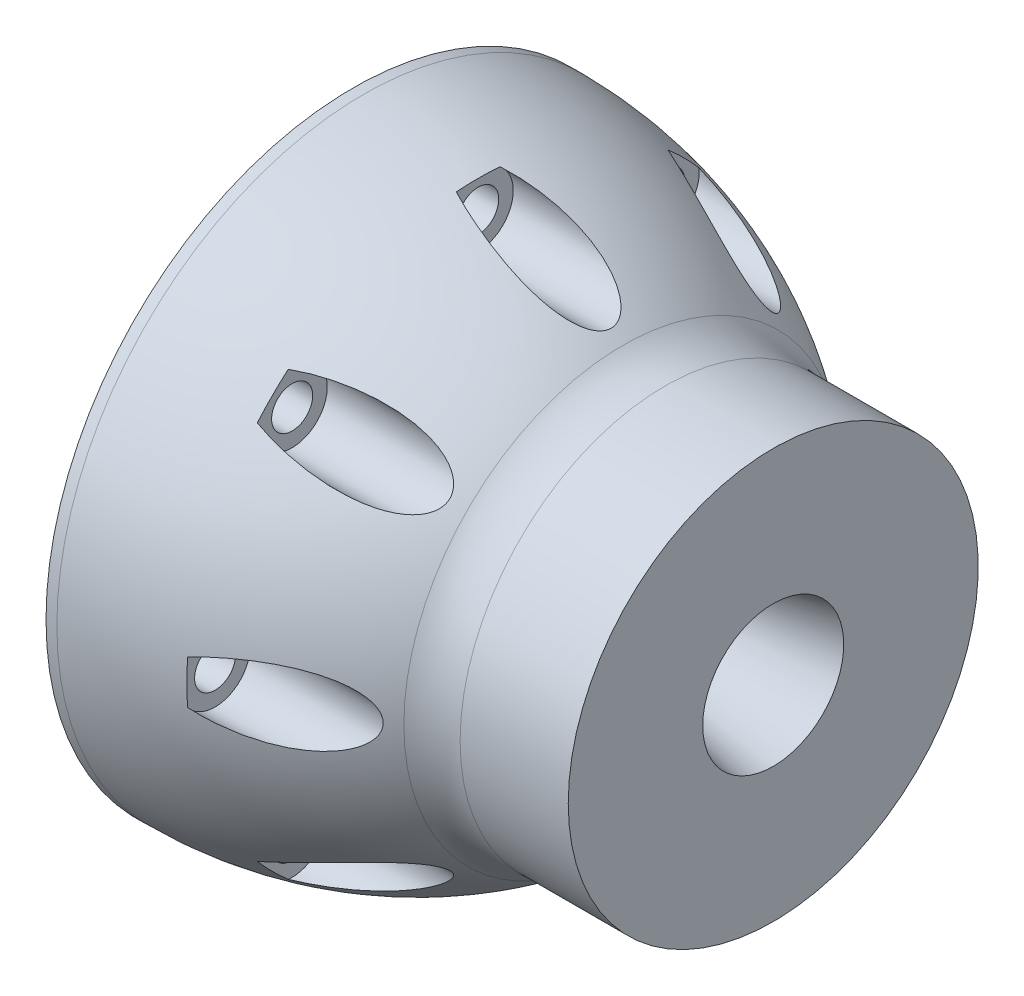
SolidWorks part; units mm, degrees
ref_plane "Front Plane" through (0, 0, 0) normal (0, 0, 1) x (1, 0, 0)
ref_plane "Top Plane" through (0, 0, 0) normal (0, 1, 0) x (1, 0, 0)
ref_plane "Right Plane" through (0, 0, 0) normal (1, 0, 0) x (0, 0, -1)
sketch "Model" plane through (0, 0, 0) normal (0, 0, 1) x (1, 0, 0)
  line L0 (0, 19.051) -> (31.9536, 19.051)
  line L1 (38.3809, 16.3887) -> (49.0299, 5.7397)
  line L2 (0, 0) -> (61.8717, 0) construction
  arc A0 (38.3809, 16.3887) -> (31.9536, 19.051) centre (31.9536, 9.9615) ccw
  arc A1 (49.0299, 5.7397) -> (50.8, 5.0065) centre (50.8, 7.5097) ccw
  arc A2 (50.8, 5.0065) -> (51.2904, 5.055) centre (50.8, 7.5097) ccw
  spline S0 degree 2 poles (51.2904, 5.055) (61.5184, 7.0984) (61.8717, 7.148) knots 0 0 0 1 1 1
  text T0 "Vortex_Chamber_Cold_Wall" font "SWTXT" height 5
sketch "Sketch2" plane through (0, 0, 0) normal (0, 0, 1) x (1, 0, 0)
  line L0 (61.8717, 7.148) -> (51.2904, 5.055)
  line L1 (49.0299, 5.7397) -> (38.3809, 16.3887)
  line L2 (31.9536, 19.051) -> (25.6036, 19.051)
  line L3 (0, 19.051) -> (31.9536, 19.051) construction
  line L4 (25.6036, 19.051) -> (25.6036, 22.225)
  line L5 (0, 0) -> (61.8717, 0) construction
  line L6 (25.6036, 22.225) -> (19.2536, 22.225)
  line L7 (19.2536, 22.225) -> (19.2536, 31.115)
  line L8 (19.2536, 31.115) -> (20.3519, 31.115)
  line L9 (50.9079, 20.7844) -> (61.8717, 20.7844)
  line L10 (61.8717, 20.7844) -> (61.8717, 7.148)
  arc A0 (51.2904, 5.055) -> (50.8, 5.0065) centre (50.7951, 7.5588) cw
  arc A1 (50.8, 5.0065) -> (49.0299, 5.7397) centre (50.7953, 7.4983) cw
  arc A2 (38.3809, 16.3887) -> (31.9536, 19.051) centre (31.9536, 9.9614) ccw
  arc A3 (20.3519, 31.115) -> (46.6468, 22.225) centre (20.3519, -12.2178) cw
  arc A4 (46.6468, 22.225) -> (50.9079, 20.7844) centre (50.9079, 27.8064) ccw
  point P21 (19.2536, 26.67)
  point P29 (41.1566, 25.4031)
  point P31 (50.307, 23.0502)
  point P32 (41.2438, 25.4903)
  point P33 (52.0499, 20.7844)
  point P34 (43.5096, 24.2702)
  point P35 (46.6468, 22.225)
  dimension "D1" = 6.35
  dimension "D2" = 22.225
  dimension "D3" = 26.67
  dimension "D4" = 6.35
revolve "Revolve1" add sketch "Sketch2" angle 360 about L2
sketch "Sketch3" plane through (19.2536, 0, 0) normal (-1, 0, 0) x (0, 0, 1)
  line L0 (0, 22.225) -> (0, 31.115) construction
  circle A0 centre (0, 26.67) radius 3.556
  circle A1 centre (0, 0) radius 22.225 construction
  circle A2 centre (0, 0) radius 22.225 construction
  circle A3 centre (0, 0) radius 31.115 construction
  point P11 (0, 26.67)
  dimension "D1" = 7.112
extrude "Cut-Extrude1" cut sketch "Sketch3" against normal up to surface (42.6182 mm away) from offset 12.7 up to face at (61.8717, 0, 20.7844) offset against normal yes
sketch "Sketch4" plane through (31.9536, 0, 0) normal (1, 0, 0) x (0, 0, -1)
  circle A0 centre (0, 26.67) radius 2.0828
  dimension "D1" = 4.1656
extrude "Cut-Extrude2" cut sketch "Sketch4" against normal up to surface (12.7 mm away) up to face at (19.2536, 0, 22.225)
pattern_circular "CirPattern1" count 8 over 360 about axis through (0, 0, 0) along (1, 0, 0) of "Cut-Extrude2", "Cut-Extrude1"
sketch "Sketch5" plane through (0, 0, 0) normal (0, 0, 1) x (1, 0, 0)
  line L0 (25.6036, 19.051) -> (-53.7714, 19.051)
  dimension "D1" = 85.725
